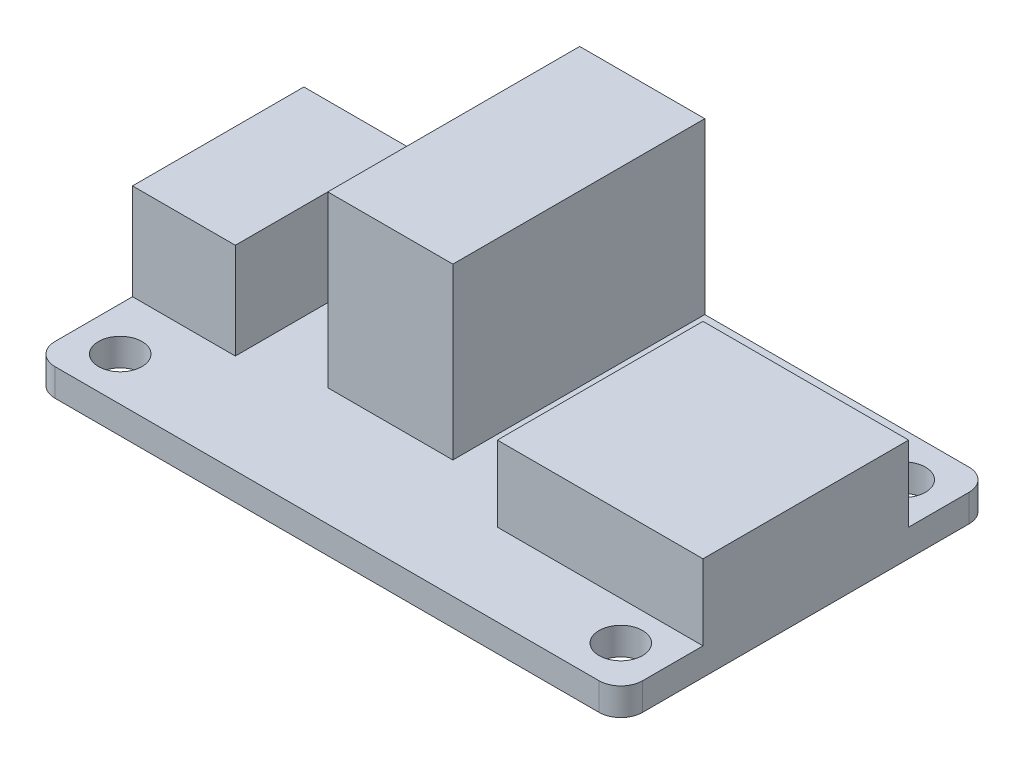
SolidWorks part; units mm, degrees
ref_plane "Front Plane" through (0, 0, 0) normal (0, 0, 1) x (1, 0, 0)
ref_plane "Top Plane" through (0, 0, 0) normal (0, 1, 0) x (1, 0, 0)
ref_plane "Right Plane" through (0, 0, 0) normal (1, 0, 0) x (0, 0, -1)
sketch "Sketch2" plane through (0, 0, 0) normal (0, 1, 0) x (1, 0, 0)
  line L0 (0, 13.284) -> (0, -12.5959) construction
  line L1 (-17.145, -10.795) -> (17.145, -10.795)
  line L2 (-17.145, -10.795) -> (-17.145, 10.795)
  line L3 (-17.145, 10.795) -> (17.145, 10.795)
  line L4 (17.145, -10.795) -> (17.145, 10.795)
  line L5 (-17.145, -10.795) -> (17.145, 10.795) construction
  line L6 (-17.145, 10.795) -> (17.145, -10.795) construction
  line L7 (-17.145, 0) -> (17.145, 0) construction
  circle A0 centre (-14.605, 8.255) radius 1.27
  circle A1 centre (14.605, 8.255) radius 1.27
  circle A2 centre (14.605, -8.255) radius 1.27
  circle A3 centre (-14.605, -8.255) radius 1.27
  point P0 (0, 0)
  dimension "D3" = 2.54
  dimension "D1" = 34.29
  dimension "D2" = 21.59
  dimension "D4" = 29.21
  dimension "D5" = 19.05
extrude "PCB" add sketch "Sketch2" along normal blind 1.6
fillet "Fillet1" radius 1.27 4 edges at (-17.145, 0.8, -10.795) (17.145, 0.8, -10.795) (17.145, 0.8, 10.795) (-17.145, 0.8, 10.795)
sketch "Sketch3" plane through (0, 1.6, 0) normal (0, 1, 0) x (1, 0, 0)
  line L0 (-17.145, 0) -> (17.145, 0) construction
  line L1 (-17.145, 9.525) -> (-17.145, -9.525) construction
  line L2 (17.145, -9.525) -> (17.145, 9.525) construction
  line L3 (15.875, 10.795) -> (-15.875, 10.795) construction
  line L4 (-17.145, 5) -> (-11.145, 5)
  line L5 (-17.145, 5) -> (-17.145, -5)
  line L6 (-17.145, -5) -> (-11.145, -5)
  line L7 (-11.145, 5) -> (-11.145, -5)
  line L8 (17.145, 6) -> (5.145, 6)
  line L9 (17.145, 6) -> (17.145, -6)
  line L10 (17.145, -6) -> (5.145, -6)
  line L11 (5.145, 6) -> (5.145, -6)
  line L12 (-6.845, 10.795) -> (0.455, 10.795)
  line L13 (-6.845, 10.795) -> (-6.845, -3.905)
  line L14 (-6.845, -3.905) -> (0.455, -3.905)
  line L15 (0.455, 10.795) -> (0.455, -3.905)
  line M13 (15.875, 10.795) -> (-15.875, 10.795)
  line M15 (-17.145, 9.525) -> (-17.145, -9.525)
  line M19 (17.145, -9.525) -> (17.145, 9.525)
  dimension "D1" = 10
  dimension "D2" = 6
  dimension "D3" = 12
  dimension "D4" = 12
  dimension "D5" = 7.3
  dimension "D6" = 14.7
  dimension "D7" = 4.3
extrude "Control_connector" add sketch "Sketch3" along normal blind 5.6 contours L0 L7 L4 M15 | L0 L5 L6 L7 region at (-14.145, 1.6, -2.5) region at (-14.145, 1.6, 2.5)
extrude "Electrode_connector" add sketch "Sketch3<3>" along normal blind 4.4 contours L11 L0 L9 L8 | L0 L11 L10 M19 region at (11.145, 1.6, -3) region at (11.145, 1.6, 3)
sketch "Sketch3<3>" plane through (0, 1.6, 0) normal (0, 1, 0) x (1, 0, 0) same geometry as "Sketch3"
extrude "Relay" add sketch "Sketch3<4>" along normal blind 9.9 contours L13 L0 L15 M13 | L0 L13 L14 L15 region at (-3.195, 1.6, -5.3975) region at (-3.195, 1.6, 1.9525)
sketch "Sketch3<4>" plane through (0, 1.6, 0) normal (0, 1, 0) x (1, 0, 0) same geometry as "Sketch3"
equation "\"D5@Sketch2\"=20.32-(\"D3@Sketch2\"/2)"
